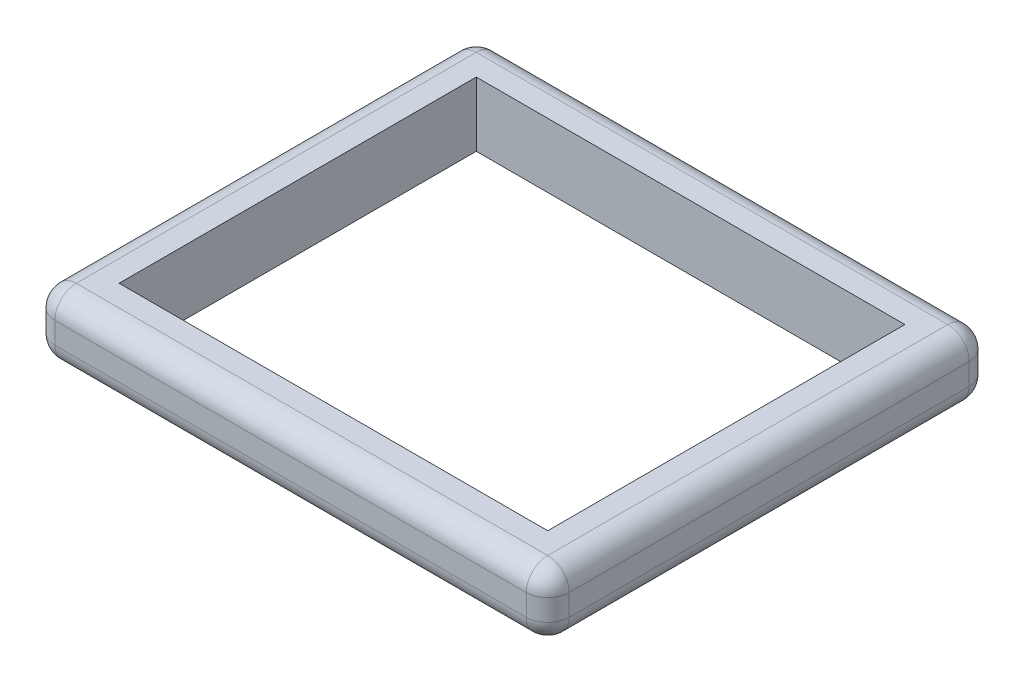
SolidWorks part; units mm, degrees
ref_plane "Front Plane" through (0, 0, 0) normal (0, 0, 1) x (1, 0, 0)
ref_plane "Top Plane" through (0, 0, 0) normal (0, 1, 0) x (1, 0, 0)
ref_plane "Right Plane" through (0, 0, 0) normal (1, 0, 0) x (0, 0, -1)
sketch "Sketch1" plane through (0, 0, 0) normal (0, 1, 0) x (1, 0, 0)
  line L5 (-381, 317.5) -> (381, 317.5)
  line L6 (-381, 317.5) -> (-381, -317.5)
  line L11 (-381, -317.5) -> (381, -317.5)
  line L12 (381, 317.5) -> (381, -317.5)
  line L13 (-381, 317.5) -> (381, -317.5) construction
  line L14 (-381, -317.5) -> (381, 317.5) construction
  line L15 (-457.2, 393.7) -> (457.2, 393.7)
  line L16 (-457.2, 393.7) -> (-457.2, -393.7)
  line L17 (-457.2, -393.7) -> (457.2, -393.7)
  line L18 (457.2, 393.7) -> (457.2, -393.7)
  line L19 (-457.2, 393.7) -> (457.2, -393.7) construction
  line L20 (-457.2, -393.7) -> (457.2, 393.7) construction
  point P0 (0, 0)
  point P1 (0, 0)
  point P5 (0, 0)
  point P8 (0, 0)
  dimension "D1" = 635
  dimension "D2" = 762
  dimension "D3" = 787.4
  dimension "D4" = 914.4
extrude "Boss-Extrude1" add sketch "Sketch1" along normal blind 114.3
sketch "Sketch3" plane through (0, 0, 317.5) normal (0, 0, -1) x (-1, 0, 0)
  line L0 (-36.0135, 74.4613) -> (65.6865, 74.4613)
  line L1 (241.3, 74.4613) -> (-241.3, 74.4613) construction
fillet "Fillet2" radius 38.1 4 edges at (457.2, 57.15, 393.7) (-457.2, 57.15, 393.7) (-457.2, 57.15, -393.7) (457.2, 57.15, -393.7)
fillet "Fillet3" radius 38.1 8 edges at (446.0408, 114.3, 382.5408) (0, 114.3, 393.7) (-446.0408, 114.3, 382.5408) (-457.2, 114.3, 0) (-446.0408, 114.3, -382.5408) (0, 114.3, -393.7) (446.0408, 114.3, -382.5408) (457.2, 114.3, 0)
fillet "Fillet4" radius 38.1 8 edges at (446.0408, 0, 382.5408) (0, 0, 393.7) (-446.0408, 0, 382.5408) (-457.2, 0, 0) (-446.0408, 0, -382.5408) (0, 0, -393.7) (446.0408, 0, -382.5408) (457.2, 0, 0)
sketch "Sketch4" plane through (0, 0, -317.5) normal (0, 0, 1) x (1, 0, 0)
  line L0 (-52.6776, 80.7058) -> (-16.7869, 80.7058) construction
  line L1 (273.05, 80.7058) -> (-273.05, 80.7058) construction
